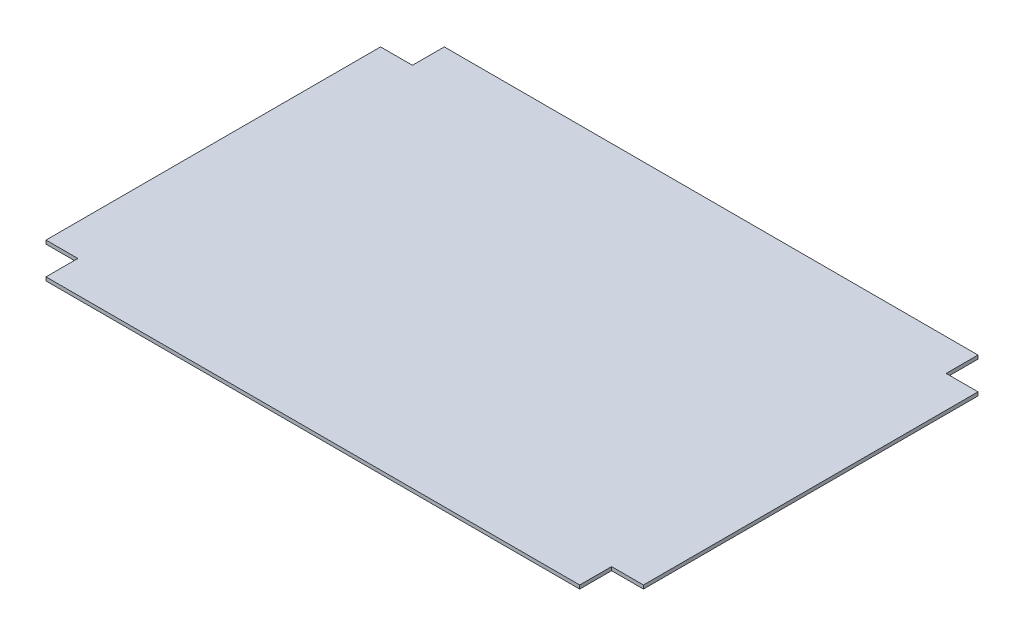
SolidWorks part; units mm, degrees
ref_plane "Front Plane" through (0, 0, 0) normal (0, 0, 1) x (1, 0, 0)
ref_plane "Top Plane" through (0, 0, 0) normal (0, 1, 0) x (1, 0, 0)
ref_plane "Right Plane" through (0, 0, 0) normal (1, 0, 0) x (0, 0, -1)
sketch "Sketch1" plane through (0, 0, 0) normal (0, 1, 0) x (1, 0, 0)
  line L0 (-670, 455) -> (-750, 455)
  line L1 (-670, -465) -> (670, -465)
  line L2 (-750, -385) -> (-750, 535)
  line L3 (-750, 535) -> (670, 535)
  line L4 (750, -385) -> (750, 455)
  line L5 (-670, -438.8028) -> (670, 438.8028) construction
  line L6 (-750, 535) -> (670, -477.9333) construction
  line L7 (-670, 455) -> (-670, 535)
  line L8 (-750, -385) -> (-670, -385)
  line L9 (-670, -385) -> (-670, -465)
  line L10 (670, -465) -> (670, -385)
  line L11 (670, -385) -> (750, -385)
  line L12 (670, 535) -> (670, 455)
  line L13 (670, 455) -> (750, 455)
  point P0 (0, 0)
  dimension "D1" = 80
  dimension "D2" = 80
  dimension "D3" = 80
  dimension "D4" = 80
  dimension "D5" = 80
  dimension "D6" = 80
  dimension "D7" = 80
  dimension "D8" = 80
  dimension "D9" = 1500
  dimension "D10" = 1000
extrude "Boss-Extrude1" add sketch "Sketch1" along normal blind 9 contours L13 L12 L3 L7 L0 L2 L8 L9 L1 L10 L11 L4 region at (0, 0, -35)
